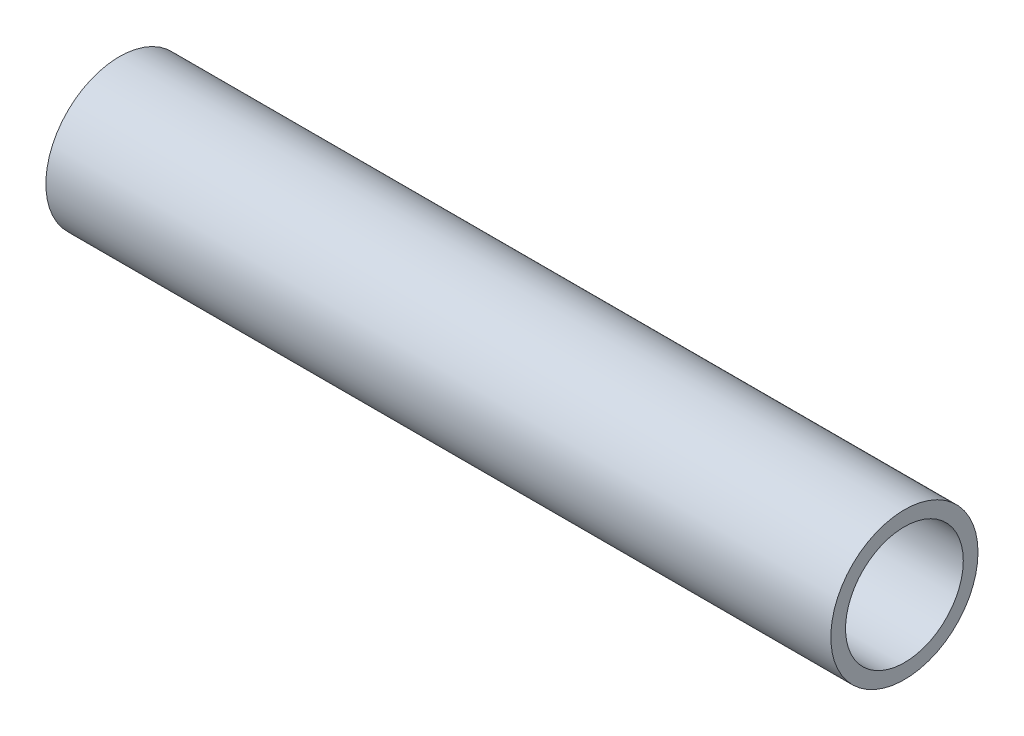
SolidWorks part; units mm, degrees
material "Plain Carbon Steel"
ref_plane "Front Plane" through (0, 0, 0) normal (0, 0, 1) x (1, 0, 0)
ref_plane "Top Plane" through (0, 0, 0) normal (0, 1, 0) x (1, 0, 0)
ref_plane "Right Plane" through (0, 0, 0) normal (1, 0, 0) x (0, 0, -1)
sketch "Sketch1" plane through (0, 0, 0) normal (1, 0, 0) x (0, 0, -1)
  circle A0 centre (0, 0) radius 7.5
  circle A1 centre (0, 0) radius 6
  dimension "D1" = 15
  dimension "D2" = 12
extrude "Boss-Extrude1" add sketch "Sketch1" along normal blind 40 and the other way blind 40
